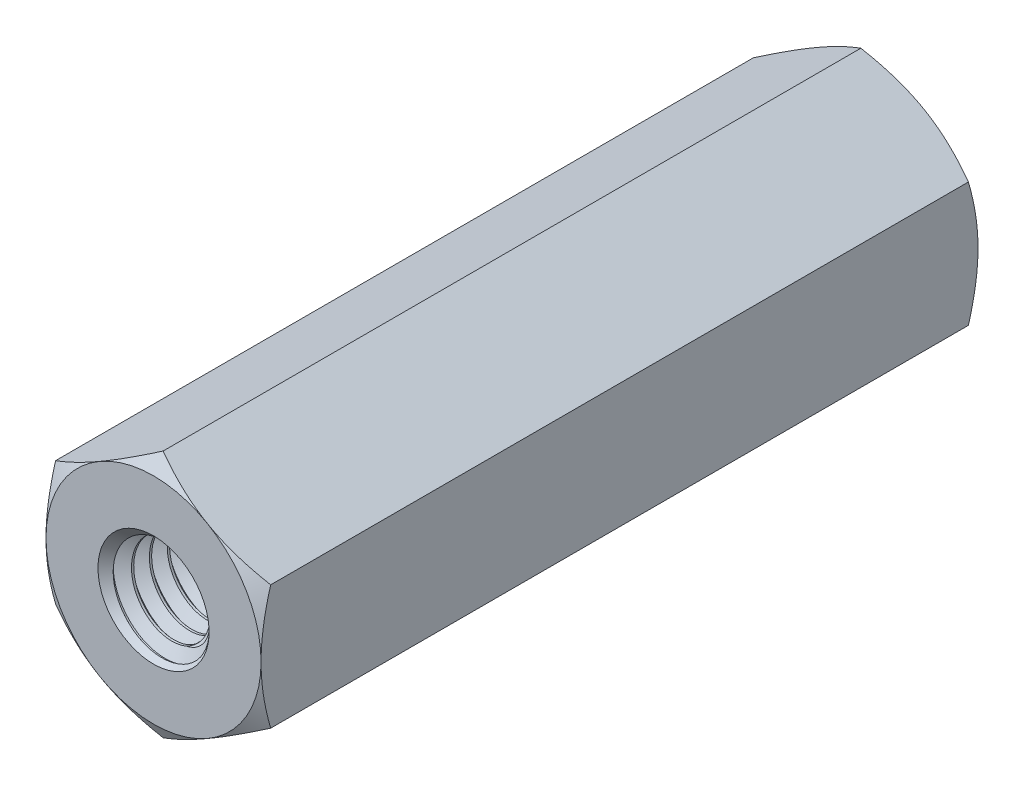
SolidWorks part; units mm, degrees
ref_plane "Front Plane" through (0, 0, 0) normal (0, 0, 1) x (1, 0, 0)
ref_plane "Top Plane" through (0, 0, 0) normal (0, 1, 0) x (1, 0, 0)
ref_plane "Right Plane" through (0, 0, 0) normal (1, 0, 0) x (0, 0, -1)
sketch "Sketch3" plane through (0, 0, 0) normal (1, 0, 0) x (0, 0, -1)
  line L0 (-10, 0) -> (10, 0) construction
  line L1 (0, 3) -> (0, -3) construction
  line L2 (-10, 1.5) -> (-10, -1.5) construction
  point P2 (5.2, 0)
  point P3 (-5.2, 0)
  dimension "Length" = 20
  dimension "Min Thread Length" = 4.8
  dimension "D1" = 4.8
  dimension "Thread Dia" = 3
  dimension "Hex" = 6
sketch "Sketch1" plane through (0, 0, 0) normal (0, 0, 1) x (1, 0, 0)
  line L1 (0, 3.4641) -> (-3, 1.7321)
  line L2 (-3, 1.7321) -> (-3, -1.7321)
  line L3 (-3, -1.7321) -> (0, -3.4641)
  line L4 (0, -3.4641) -> (3, -1.7321)
  line L5 (3, -1.7321) -> (3, 1.7321)
  line L6 (3, 1.7321) -> (0, 3.4641)
  circle A0 centre (0, 0) radius 3 construction
  circle A1 centre (0, 0) radius 1.5
extrude "Extrude1" add sketch "Sketch1" along normal up to vertex (10 mm away) and the other way up to vertex (10 mm away) up to point (0, 0, 10) other way up to point (0, 0, -10)
sketch "Sketch11" plane through (0, 0, -10) normal (0, 0, -1) x (-1, 0, 0)
  circle A0 centre (0, 0) radius 1.5 construction
  circle A1 centre (0, 0) radius 1.5
curve "Helix/Spiral1" pitch 0.5 height 20.5 turns 41 parameters "Pitch"=0.5
sketch "Sketch12" plane through (0, 0, 0) normal (1, 0, 0) x (0, 0, -1)
  line L0 (10.4375, 1.5) -> (10, 1.5)
  line L1 (10.4375, 1.5) -> (10.25, 1.1752)
  line L2 (10.25, 1.1752) -> (10.1875, 1.1752)
  line L3 (10.1875, 1.1752) -> (10, 1.5)
  line L4 (10.2188, 1.1752) -> (10.2188, 1.5) construction
  line L5 (10.3438, 1.3376) -> (10.0938, 1.3376) construction
  dimension "D1" = 0.0625
  dimension "D2" = 0.25
  dimension "D3" = 60
sweep "Sweep1" add profiles "Sketch12" path "Helix/Spiral1"
sketch "Sketch6" plane through (0, 0, -10) normal (0, 0, -1) x (-1, 0, 0)
  line L6 (0, 3.4641) -> (-3, 1.7321)
  line L7 (-3, 1.7321) -> (-3, -1.7321)
  line L8 (-3, -1.7321) -> (0, -3.4641)
  line L9 (0, -3.4641) -> (3, -1.7321)
  line L10 (3, -1.7321) -> (3, 1.7321)
  line L11 (3, 1.7321) -> (0, 3.4641)
  line L12 (0, 3.4641) -> (-3, 1.7321)
  line L13 (-3, 1.7321) -> (-3, -1.7321)
  line L14 (-3, -1.7321) -> (0, -3.4641)
  line L15 (0, -3.4641) -> (3, -1.7321)
  line L16 (3, -1.7321) -> (3, 1.7321)
  line L17 (3, 1.7321) -> (0, 3.4641)
  dimension "D1" = 0
extrude "Extrude2" cut sketch "Sketch6" along normal through all
sketch "Sketch7" plane through (0, 0, -10) normal (0, 0, -1) x (-1, 0, 0)
  circle A2 centre (0, 0) radius 1.5508
  circle A3 centre (0, 0) radius 1.5508
  dimension "D1" = 0.0508
extrude "Extrude3" cut sketch "Sketch7" against normal through all draft 43
sketch "Sketch8" plane through (0, 0, -10) normal (0, 0, -1) x (-1, 0, 0)
  circle A0 centre (0, 0) radius 3 construction
  circle A1 centre (0, 0) radius 3
extrude "Extrude4" cut sketch "Sketch8" against normal through all draft 60 flip side to cut
mirror "Mirror1" about plane through (0, 0, 0) normal (0, 0, 1) of "Extrude2", "Extrude3", "Extrude4"
sketch "Sketch9" [suppressed] plane through (0, 0, 0) normal (1, 0, 0) x (0, 0, -1)
  line L1 (-1.2, 1.1353) -> (1.2, 1.1353)
  line L2 (-1.2, 1.1353) -> (-1.2, 0)
  line L3 (-1.2, 0) -> (1.2, 0)
  line L4 (1.2, 1.1353) -> (1.2, 0)
  line L7 (-6, 0) -> (6, 0) construction
revolve "Revolve" [suppressed] add sketch "Sketch9" angle 360 about L0
sketch "Sketch10" [suppressed] plane through (0, 0, 0) normal (1, 0, 0) x (0, 0, -1)
  line L0 (6, 1.25) -> (1.2, 1.25)
  line L1 (-6, 1.25) -> (-1.2, 1.25)
  line L2 (1.2, 1.25) -> (1.2, -1.25)
  line L3 (-6, -1.25) -> (-1.2, -1.25)
  line L4 (-1.2, 1.25) -> (-1.2, -1.25)
  line L5 (1.2, -1.25) -> (6, -1.25)
equation "\"D1@Sketch3\" = \"Min Thread Length@Sketch3\""
equation "\"D3@Helix/Spiral1\" = \"Length@Sketch3\"+\"Pitch@Helix/Spiral1\""
equation "\"D1@Sketch12\" = \"Pitch@Helix/Spiral1\"*.125"
equation "\"D2@Sketch12\" = \"Pitch@Helix/Spiral1\"*.5"
